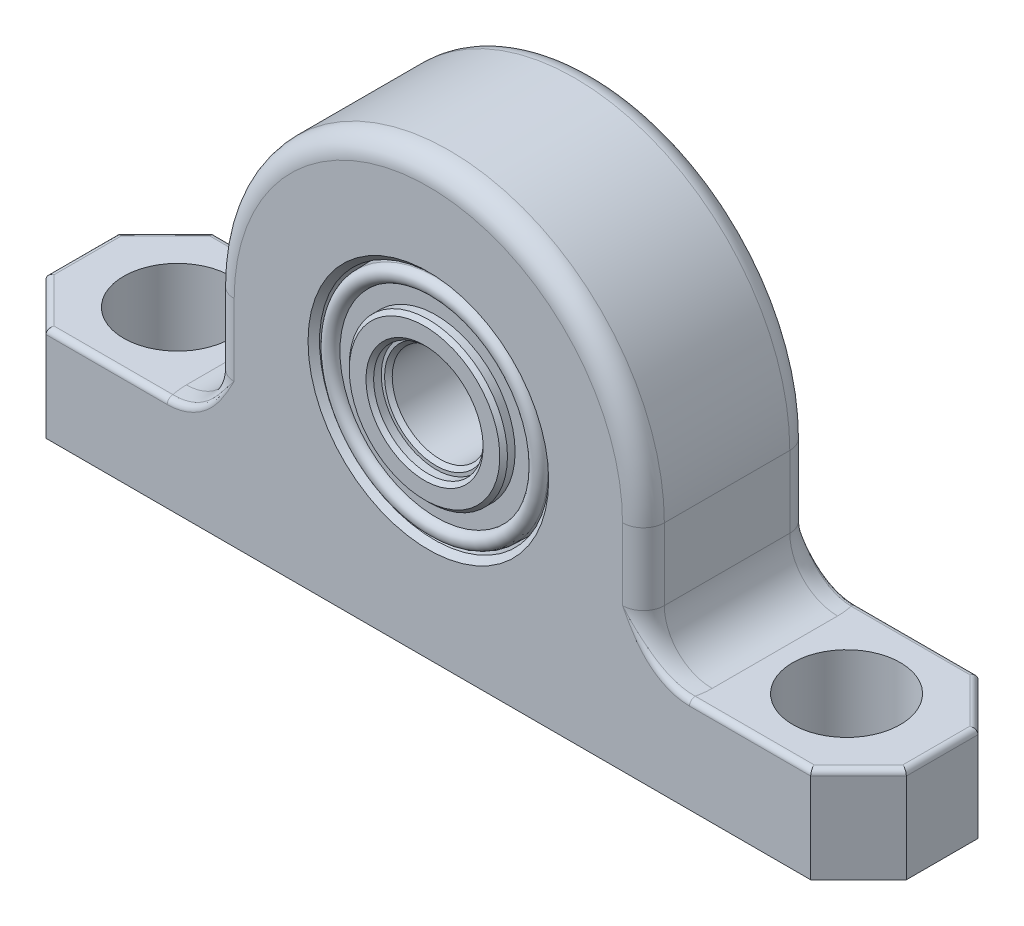
SolidWorks part; units mm, degrees
ref_plane "Front Plane" through (0, 0, 0) normal (0, 0, 1) x (1, 0, 0)
ref_plane "Top Plane" through (0, 0, 0) normal (0, 1, 0) x (1, 0, 0)
ref_plane "Right Plane" through (0, 0, 0) normal (1, 0, 0) x (0, 0, -1)
sketch "Sketch1" plane through (0, 0, 0) normal (0, 0, 1) x (1, 0, 0)
  line L0 (-28.575, 0) -> (28.575, 0)
  line L1 (28.575, 0) -> (28.575, 6.35)
  line L2 (-28.575, 0) -> (-28.575, 6.35)
  line L3 (-28.575, 6.35) -> (-14.2875, 6.35)
  line L4 (28.575, 6.35) -> (14.2875, 6.35)
  line L5 (-14.2875, 6.35) -> (-14.2875, 14.2875)
  line L6 (14.2875, 6.35) -> (14.2875, 14.2875)
  line L7 (0, 0) -> (0, 28.575) construction
  line L8 (2.2361, 16.5236) -> (10.1028, 24.3903) construction
  circle A0 centre (0, 14.2875) radius 3.1623
  arc A1 (14.2875, 14.2875) -> (-14.2875, 14.2875) centre (0, 14.2875) ccw
  circle A2 centre (0, 14.2875) radius 7.6124 construction
  point P16 (5.3828, 19.6703)
  point P17 (0, 17.4498)
  point P18 (0, 21.8999)
  dimension "D1" = 45
  dimension "ID" = 6.3246
  dimension "Overall Height" = 28.575
  dimension "Overall Length" = 57.15
  dimension "CAD B" = 6.35
  dimension "Center Height" = 14.2875
  dimension "D2" = 11.1252
  dimension "D3" = 4.4501
sketch "Sketch2" plane through (0, 0, 0) normal (0, 1, 0) x (1, 0, 0)
  line L0 (-22.225, 0) -> (22.225, 0) construction
  line L1 (-28.575, -5.5562) -> (28.575, 5.5562) construction
  line L2 (-28.575, 5.5562) -> (28.575, 5.5562)
  line L3 (-28.575, 5.5562) -> (-28.575, -5.5562)
  line L4 (-28.575, -5.5562) -> (28.575, -5.5562)
  line L5 (28.575, 5.5562) -> (28.575, -5.5562)
  circle A0 centre (-22.225, 0) radius 3.5719
  circle A1 centre (22.225, 0) radius 3.5719
  dimension "Mounting Hole" = 7.1437
  dimension "Mounting Center" = 44.45
  dimension "Overall Width" = 11.1125
sketch "Sketch3" plane through (0, 0, 0) normal (0, 0, 1) x (1, 0, 0)
  line L0 (-28.575, 0) -> (-28.575, 6.35) construction
  line L1 (-28.575, 0) -> (28.575, 0) construction
  line L2 (-28.575, 6.35) -> (-14.2875, 6.35) construction
  line L3 (28.575, 6.35) -> (14.2875, 6.35) construction
  line L4 (28.575, 0) -> (28.575, 6.35) construction
  line L5 (14.2875, 6.35) -> (14.2875, 14.2875) construction
  line L6 (-14.2875, 6.35) -> (-14.2875, 14.2875) construction
  line L7 (-28.575, 0) -> (-28.575, 6.35)
  line L8 (-28.575, 0) -> (28.575, 0)
  line L9 (-28.575, 6.35) -> (-14.2875, 6.35)
  line L10 (28.575, 6.35) -> (14.2875, 6.35)
  line L11 (28.575, 0) -> (28.575, 6.35)
  line L12 (14.2875, 6.35) -> (14.2875, 14.2875)
  line L13 (-14.2875, 6.35) -> (-14.2875, 14.2875)
  arc A0 (14.2875, 14.2875) -> (-14.2875, 14.2875) centre (0, 14.2875) ccw construction
  circle A1 centre (0, 14.2875) radius 7.6124 construction
  arc A2 (14.2875, 14.2875) -> (-14.2875, 14.2875) centre (0, 14.2875) ccw
  circle A3 centre (0, 14.2875) radius 7.6124
extrude "Boss-Extrude1" add sketch "Sketch3" against normal up to vertex (5.5563 mm away) and the other way up to vertex (5.5563 mm away) up to point (-28.575, 0, -5.5562) other way up to point (-28.575, 0, 5.5562)
sketch "Sketch4" plane through (0, 0, 0) normal (0, 1, 0) x (1, 0, 0)
  circle A0 centre (-22.225, 0) radius 3.5719 construction
  circle A1 centre (22.225, 0) radius 3.5719 construction
  circle A2 centre (-22.225, 0) radius 3.5719
  circle A3 centre (22.225, 0) radius 3.5719
extrude "Cut-Extrude1" cut sketch "Sketch4" along normal through all
chamfer "Chamfer1" distance 3.175 angle 45 4 edges at (-28.575, 3.175, -5.5562) (28.575, 3.175, 5.5562) (28.575, 3.175, -5.5562) (-28.575, 3.175, 5.5562)
fillet "Fillet1" radius 1.3891 6 edges at (-14.2875, 10.3188, -5.5562) (0, 28.575, -5.5562) (-14.2875, 10.3188, 5.5562) (0, 28.575, 5.5562) (14.2875, 10.3187, -5.5562) (14.2875, 10.3187, 5.5562)
fillet "Fillet2" radius 3.175 6 edges at (-13.8807, 6.35, -5.1494) (-13.8807, 6.35, 5.1494) (13.8807, 6.35, -5.1494) (13.8807, 6.35, 5.1494) (-14.2875, 6.35, 0) (14.2875, 6.35, 0)
chamfer "Chamfer2" distance 0.381 angle 45 2 edges at (7.6124, 14.2875, 5.5562) (7.6124, 14.2875, -5.5562)
fillet "Fillet3" radius 0.381 14 edges at (-15.0119, 7.0879, -5.5562) (-15.0119, 7.0879, 5.5562) (15.0119, 7.0879, -5.5562) (15.0119, 7.0879, 5.5562) (-21.323, 6.35, -5.5562) (-26.9875, 6.35, -3.9687) (-28.575, 6.35, 0) (-26.9875, 6.35, 3.9687) (-21.323, 6.35, 5.5563) (21.323, 6.35, -5.5562) (26.9875, 6.35, -3.9687) (28.575, 6.35, 0) (26.9875, 6.35, 3.9687) (21.323, 6.35, 5.5563)
sketch "Sketch5" plane through (0, 0, 0) normal (1, 0, 0) x (0, 0, -1)
  line L1 (-5.5562, 21.8999) -> (5.5562, 21.8999)
  line L2 (-5.5562, 21.8999) -> (-5.5562, 17.4498)
  line L3 (-5.5562, 17.4498) -> (5.5562, 17.4498)
  line L4 (5.5562, 21.8999) -> (5.5562, 17.4498)
sketch "Sketch6" plane through (0, 0, 0) normal (1, 0, 0) x (0, 0, -1)
  line L0 (0, 21.8999) -> (5.5562, 21.8999)
  line L1 (-5.5562, 21.8999) -> (5.5562, 21.8999) construction
  line L2 (0, 21.8999) -> (-5.0484, 21.7236)
  line L3 (-5.5562, 21.8999) -> (-5.5562, 17.4498) construction
  line L4 (-5.0482, 20.6717) -> (-5.0482, 19.5424)
  line L5 (-5.0482, 19.5424) -> (-5.8102, 19.5424)
  line L6 (-5.8102, 19.5424) -> (-5.8102, 17.9241)
  line L7 (-5.8102, 17.9241) -> (-5.0483, 17.9241)
  line L8 (-5.0483, 17.9241) -> (-5.0483, 17.4498)
  line L9 (-5.5562, 17.4498) -> (5.5562, 17.4498) construction
  line L10 (-5.0483, 17.4498) -> (3.5242, 17.4498)
  line L11 (5.5562, 21.8999) -> (5.5562, 20.6717)
  line L12 (5.5562, 21.8999) -> (5.5562, 17.4498) construction
  line L13 (5.5562, 20.6717) -> (1.7462, 20.6717)
  line L14 (1.7462, 20.6717) -> (1.7462, 19.5424)
  line L15 (1.7462, 19.5424) -> (4.2862, 19.5424)
  line L16 (4.2862, 19.5424) -> (4.2862, 17.9241)
  line L17 (4.2862, 17.9241) -> (3.5242, 17.9241)
  line L18 (3.5242, 17.9241) -> (3.5242, 17.4498)
  line L20 (-5.5562, 14.2875) -> (5.5562, 14.2875) construction
  line L21 (-5.5562, 0) -> (-5.5562, 5.969) construction
  arc A0 (-5.0484, 21.7236) -> (-5.0482, 20.6717) centre (-5.03, 21.1977) ccw
  dimension "D2" = 0.254
  dimension "D1" = 2
  dimension "D3" = 0.762
  dimension "D4" = 4.4501
  dimension "D5" = 1.27
  dimension "D6" = 2.54
  dimension "D7" = 1.6182
  dimension "D8" = 1.0518
  dimension "D9" = 7.2733
revolve "Revolve1" add sketch "Sketch6" angle 360 about L20
chamfer "Chamfer3" distance 0.254 angle 45 6 edges at (3.6366, 14.2875, -4.2862) (5.2549, 14.2875, -4.2862) (3.1623, 14.2875, 5.0483) (3.1623, 14.2875, -3.5242) (5.2549, 14.2875, 5.8102) (3.6366, 14.2875, 5.8102)
equation "\"D3@Sketch1\"=\"D2@Sketch1\"/2.50"
equation "\"D1@Fillet1\"=\"Overall Width@Sketch2\"/8"
equation "\"D7@Sketch6\"=\"D4@Sketch6\"/2.750"
equation "\"D8@Sketch6\"=\"D7@Sketch6\"*.65"
equation "\"D9@Sketch6\"=\"ID@Sketch1\"*1.15"
